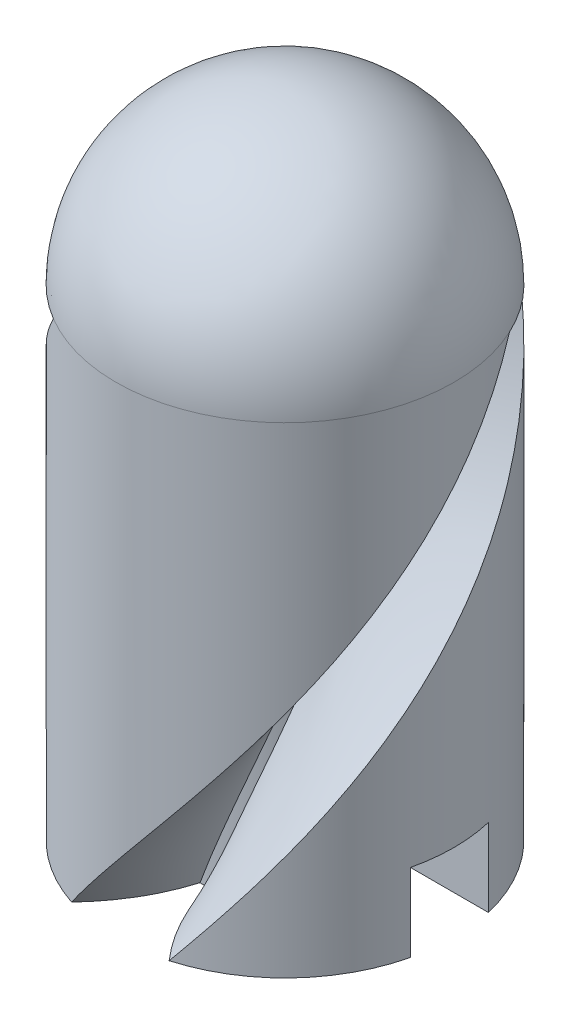
SolidWorks part; units mm, degrees
ref_plane "Front Plane" through (0, 0, 0) normal (0, 0, 1) x (1, 0, 0)
ref_plane "Top Plane" through (0, 0, 0) normal (0, 1, 0) x (1, 0, 0)
ref_plane "Right Plane" through (0, 0, 0) normal (1, 0, 0) x (0, 0, -1)
sketch "Sketch3" plane through (0, 0, 0) normal (0, 1, 0) x (-1, 0, 0)
  circle A0 centre (0, 0) radius 6.5
  dimension "D1" = 13
extrude "Boss-Extrude3" add sketch "Sketch3" along normal blind 18.5
thread "Thread4" pitch 6.35 method cut profile "Thread Profile6" start angle 250, offset 5, length 0, pitch 50, diameter 13
ref_plane "Plane6" through (-2.2231, -5, 6.108) normal (0.9397, 0, 0.342) x (0.342, 0, -0.9397)
sketch "Thread Profile6" plane through (-2.2231, -5, 6.108) normal (0.9397, 0, 0.342) x (0.342, 0, -0.9397)
  line L0 (0, 0) -> (0, 6.35) construction
  line L1 (0, 0) -> (3.437, 1.9844)
  line L2 (3.437, 1.9844) -> (3.437, 2.7781)
  line L3 (3.437, 2.7781) -> (0, 4.7625)
  line L4 (3.437, 2.3812) -> (0, 2.3812) construction
  line L11 (0, 0) -> (0, 4.7625)
  point P2 (0, 0)
  dimension "Pitch" = 6.35
  dimension "Profile_Angle" = 60
  dimension "Profile_Land" = 0.7937
  dimension "Profile_Height" = 3.437
thread "Thread6" pitch 6.35 method cut profile "Thread Profile8" start angle 70, offset 5, length 0, pitch 50, diameter 13
ref_plane "Plane8" through (2.2231, -5, -6.108) normal (-0.9397, 0, -0.342) x (-0.342, 0, 0.9397)
sketch "Thread Profile8" plane through (2.2231, -5, -6.108) normal (-0.9397, 0, -0.342) x (-0.342, 0, 0.9397)
  line L0 (0, 0) -> (0, 6.35) construction
  line L1 (0, 0) -> (3.437, 1.9844)
  line L2 (3.437, 1.9844) -> (3.437, 2.7781)
  line L3 (3.437, 2.7781) -> (0, 4.7625)
  line L4 (3.437, 2.3812) -> (0, 2.3812) construction
  line L11 (0, 0) -> (0, 4.7625)
  point P2 (0, 0)
  dimension "Pitch" = 6.35
  dimension "Profile_Angle" = 60
  dimension "Profile_Land" = 0.7937
  dimension "Profile_Height" = 3.437
sketch "Sketch5" plane through (0, 0, 0) normal (0, -1, 0) x (1, 0, 0)
  line L1 (-6.5, 0) -> (0, -6.5)
  line L2 (0, -6.5) -> (6.5, 0)
  circle A0 centre (0, 0) radius 6.5 construction
  arc A1 (-6.5, 0) -> (6.5, 0) centre (0, 0) ccw
  arc M4 (-2.0393, 6.1718) -> (-1.7913, -6.2483) centre (0, 0) ccw
extrude "Cut-Extrude2" [suppressed] cut sketch "Sketch5" against normal blind 3 contours L1 M4 | L2 M4
sketch "Sketch7" plane through (0, 18.5, 0) normal (0, 1, 0) x (1, 0, 0)
  line L0 (-6.5, 0) -> (6.5, 0)
  arc A0 (6.5, 0) -> (-6.5, 0) centre (0, 0) ccw
  dimension "D1" = 13
revolve "Revolve1" add sketch "Sketch7" angle 180 about L0
sketch "Sketch8" plane through (0, 0, 0) normal (0, -1, 0) x (1, 0, 0)
  line L0 (0, 6.7104) -> (0, -6.9817) construction
  line L1 (-6.8102, 1.5) -> (-3, 1.5)
  line L2 (-6.8102, 1.5) -> (-6.8102, -1.5)
  line L3 (-6.8102, -1.5) -> (-3, -1.5)
  line L4 (-3, 1.5) -> (-3, -1.5)
  line L5 (3, 1.5) -> (3, -1.5)
  line L6 (6.8102, -1.5) -> (3, -1.5)
  line L7 (6.8102, 1.5) -> (6.8102, -1.5)
  line L8 (6.8102, 1.5) -> (3, 1.5)
  dimension "D1" = 3
  dimension "D2" = 1.5
  dimension "D3" = 3
extrude "Cut-Extrude3" cut sketch "Sketch8" against normal blind 3
